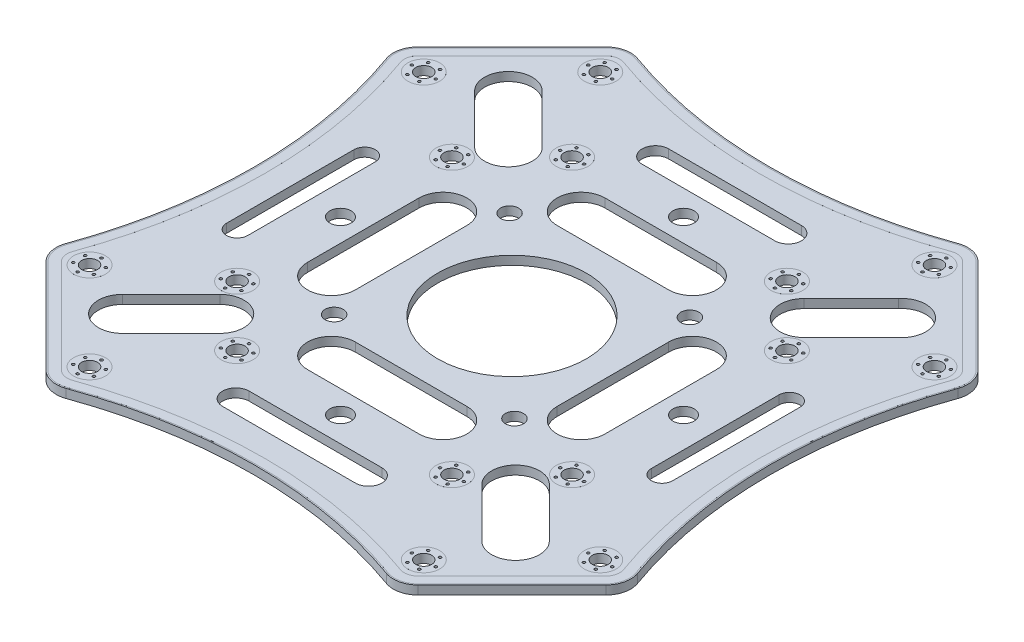
SolidWorks part; units mm, degrees
material "PLA"
ref_plane "Front Plane" through (0, 0, 0) normal (0, 0, 1) x (1, 0, 0)
ref_plane "Top Plane" through (0, 0, 0) normal (0, 1, 0) x (1, 0, 0)
ref_plane "Right Plane" through (0, 0, 0) normal (1, 0, 0) x (0, 0, -1)
sketch "Sketch1" plane through (0, 0, 0) normal (0, 1, 0) x (1, 0, 0)
  line L0 (-48.55, 0) -> (48.55, 0) construction
  line L1 (0, 48.55) -> (0, -48.55) construction
  line L2 (-30.1605, 53.8) -> (30.1605, 53.8) construction
  line L3 (0, 48.55) -> (0, 53.8) construction
  line L4 (-53.8, 30.1605) -> (-53.8, -30.1605) construction
  line L5 (-30.1605, -53.8) -> (30.1605, -53.8) construction
  line L6 (53.8, -30.1605) -> (53.8, 30.1605) construction
  line L7 (35.0464, 52.7056) -> (52.7056, 35.0464)
  line L8 (-52.7056, 35.0464) -> (-35.0464, 52.7056)
  line L9 (-52.7056, -35.0464) -> (-35.0464, -52.7056)
  line L10 (35.0464, -52.7056) -> (52.7056, -35.0464)
  line L11 (-43.876, -43.876) -> (43.876, 43.876) construction
  line L12 (-43.876, 43.876) -> (43.876, -43.876) construction
  line L13 (-31.7403, 54.075) -> (-31.7403, -54.075) construction
  line L14 (-31.7403, -54.075) -> (31.7403, -54.075) construction
  arc A0 (-30.1605, 53.8) -> (30.1605, 53.8) centre (0, 137.8088) ccw
  arc A1 (53.8, 30.1605) -> (53.8, -30.1605) centre (137.8088, 0) ccw
  arc A2 (30.1605, -53.8) -> (-30.1605, -53.8) centre (0, -137.8088) ccw
  arc A3 (-53.8, -30.1605) -> (-53.8, 30.1605) centre (-137.8088, 0) ccw
  arc A4 (-53.8, -30.1605) -> (-52.7056, -35.0464) centre (-49.3995, -31.7403) ccw
  arc A5 (-35.0464, -52.7056) -> (-30.1605, -53.8) centre (-31.7403, -49.3995) ccw
  arc A6 (30.1605, -53.8) -> (35.0464, -52.7056) centre (31.7403, -49.3995) ccw
  arc A7 (52.7056, -35.0464) -> (53.8, -30.1605) centre (49.3995, -31.7403) ccw
  arc A8 (53.8, 30.1605) -> (52.7056, 35.0464) centre (49.3995, 31.7403) ccw
  arc A9 (35.0464, 52.7056) -> (30.1605, 53.8) centre (31.7403, 49.3995) ccw
  arc A10 (-30.1605, 53.8) -> (-35.0464, 52.7056) centre (-31.7403, 49.3995) ccw
  arc A11 (-52.7056, 35.0464) -> (-53.8, 30.1605) centre (-49.3995, 31.7403) ccw
  point P2 (0, 0)
  point P6 (0, 0)
  point P34 (0, 0)
  dimension "D2" = 108.15
  dimension "D4" = 124.1
  dimension "D1" = 97.1
  dimension "D3" = 5.25
  dimension "D5" = 45
extrude "Boss-Extrude1" add sketch "Sketch1" along normal blind 0.825 and the other way blind 0.825
sketch "Sketch2" plane through (0, 0.825, 0) normal (0, 1, 0) x (1, 0, 0)
  line L0 (-12.5, -42) -> (12.5, -42)
  line L1 (-12.5, -37) -> (12.5, -37)
  line L2 (-10.5, -28) -> (10.5, -28)
  line L3 (-10.5, -19) -> (10.5, -19)
  line L4 (28, -10.5) -> (28, 10.5)
  line L5 (19, 10.5) -> (19, -10.5)
  line L6 (38, -11.7556) -> (38, 12.2444)
  line L7 (42, -11.7556) -> (42, 12.2444)
  line L8 (0, 0) -> (48.998, 0) construction
  line L9 (0, 0) -> (0, -48.55) construction
  line L10 (-10.5, 19) -> (10.5, 19)
  line L11 (-10.5, 28) -> (10.5, 28)
  line L12 (-12.5, 37) -> (12.5, 37)
  line L13 (-12.5, 42) -> (12.5, 42)
  line L14 (-42, -11.7556) -> (-42, 12.2444)
  line L15 (-38, -11.7556) -> (-38, 12.2444)
  line L16 (-19, 10.5) -> (-19, -10.5)
  line L17 (-28, -10.5) -> (-28, 10.5)
  line L18 (-33.8434, -39.5307) -> (-24.651, -30.3383)
  line L19 (-40.2073, -33.1667) -> (-31.0149, -23.9744)
  line L20 (24.654, -30.3413) -> (33.6832, -39.362)
  line L21 (31.0149, -23.9744) -> (40.2073, -33.1667)
  line L22 (33.546, 39.2333) -> (24.651, 30.3383)
  line L23 (-40.2073, 33.1667) -> (-31.0149, 23.9744)
  line L24 (31.0149, 23.9744) -> (39.9099, 32.8694)
  line L26 (-24.651, 30.3383) -> (-33.8434, 39.5307)
  arc A0 (12.5, -42) -> (12.5, -37) centre (12.5, -39.5) ccw
  arc A1 (-12.5, -37) -> (-12.5, -42) centre (-12.5, -39.5) ccw
  arc A2 (-10.5, -19) -> (-10.5, -28) centre (-10.5, -23.5) ccw
  arc A3 (10.5, -28) -> (10.5, -19) centre (10.5, -23.5) ccw
  arc A4 (38, -11.7556) -> (42, -11.7556) centre (40, -11.7556) ccw
  arc A5 (19, -10.5) -> (28, -10.5) centre (23.5, -10.5) ccw
  arc A6 (42, 12.2444) -> (38, 12.2444) centre (40, 12.2444) ccw
  arc A7 (28, 10.5) -> (19, 10.5) centre (23.5, 10.5) ccw
  arc A8 (53.943, 29.5883) -> (53.943, -29.5883) centre (139.9907, 0) ccw construction
  arc A9 (30.1605, -53.8) -> (-30.1605, -53.8) centre (0, -137.8088) ccw construction
  arc A10 (10.5, 28) -> (10.5, 19) centre (10.5, 23.5) cw
  arc A11 (-10.5, 19) -> (-10.5, 28) centre (-10.5, 23.5) cw
  arc A12 (-12.5, 37) -> (-12.5, 42) centre (-12.5, 39.5) cw
  arc A13 (12.5, 42) -> (12.5, 37) centre (12.5, 39.5) cw
  arc A14 (-28, 10.5) -> (-19, 10.5) centre (-23.5, 10.5) cw
  arc A15 (-42, 12.2444) -> (-38, 12.2444) centre (-40, 12.2444) cw
  arc A16 (-19, -10.5) -> (-28, -10.5) centre (-23.5, -10.5) cw
  arc A17 (-38, -11.7556) -> (-42, -11.7556) centre (-40, -11.7556) cw
  arc A18 (-24.651, -30.3383) -> (-31.0149, -23.9744) centre (-27.833, -27.1563) ccw
  arc A19 (-40.2073, -33.1667) -> (-33.8434, -39.5307) centre (-37.0253, -36.3487) ccw
  arc A20 (33.6832, -39.362) -> (40.2073, -33.1667) centre (37.0253, -36.3487) ccw
  arc A21 (31.0149, -23.9744) -> (24.654, -30.3413) centre (27.833, -27.1563) ccw
  arc A22 (-31.0149, 23.9744) -> (-24.651, 30.3383) centre (-27.833, 27.1563) ccw
  arc A23 (-33.8434, 39.5307) -> (-40.2073, 33.1667) centre (-37.0253, 36.3487) ccw
  arc A24 (39.9099, 32.8694) -> (33.546, 39.2333) centre (37.0253, 36.3487) ccw
  arc A25 (24.651, 30.3383) -> (31.0149, 23.9744) centre (27.833, 27.1563) ccw
  circle A26 centre (0, 0) radius 14
extrude "Cut-Extrude1" cut sketch "Sketch2" against normal up to surface (1.65 mm away) up to face at (0, -0.825, 0)
sketch "Sketch3" plane through (0, 0.825, 0) normal (0, 1, 0) x (1, 0, 0)
  line L0 (-48.0833, -31.4663) -> (-31.4663, -48.0833) construction
  line L1 (-52.7056, -35.0464) -> (-35.0464, -52.7056) construction
  line L2 (-39.7748, -39.7748) -> (-43.876, -43.876) construction
  line L3 (43.876, -43.876) -> (39.7748, -39.7748) construction
  line L4 (31.4663, -48.0833) -> (48.0833, -31.4663) construction
  line L5 (43.876, 43.876) -> (39.7748, 39.7748) construction
  line L6 (31.4663, 48.0833) -> (48.0833, 31.4663) construction
  line L7 (-43.876, 43.876) -> (-39.7748, 39.7748) construction
  line L8 (-31.4663, 48.0833) -> (-48.0833, 31.4663) construction
  line L9 (-35.0464, 52.7056) -> (-52.7056, 35.0464) construction
  line L10 (52.7056, 35.0464) -> (35.0464, 52.7056) construction
  line L11 (35.0464, -52.7056) -> (52.7056, -35.0464) construction
  line L12 (-31.5403, -20.2266) -> (-20.2266, -31.5403) construction
  line L13 (31.5403, -20.2266) -> (20.2266, -31.5403) construction
  line L14 (-31.5403, 20.2266) -> (-20.2266, 31.5403) construction
  line L15 (20.2266, 31.5403) -> (31.5403, 20.2266) construction
  line L16 (-25.8834, -25.8834) -> (-39.7748, -39.7748) construction
  line L17 (-39.7748, 39.7748) -> (-25.8834, 25.8834) construction
  line L18 (39.7748, 39.7748) -> (25.8834, 25.8834) construction
  line L19 (25.8834, -25.8834) -> (39.7748, -39.7748) construction
  line L20 (-20.2266, -31.5403) -> (-31.4663, -48.0833) construction
  line L21 (-31.5403, -20.2266) -> (-48.0833, -31.4663) construction
  line L22 (0, 0) -> (-24.651, 23.9744) construction
  line L23 (0, 0) -> (24.651, 23.9744) construction
  line L24 (0, 0) -> (24.6495, -23.9759) construction
  line L25 (0, 0) -> (-24.651, -23.9744) construction
  circle A0 centre (-48.0833, -31.4663) radius 1.5
  circle A1 centre (-31.4663, -48.0833) radius 1.5
  circle A2 centre (31.4663, -48.0833) radius 1.5
  circle A3 centre (48.0833, -31.4663) radius 1.5
  circle A4 centre (48.0833, 31.4663) radius 1.5
  circle A5 centre (31.4663, 48.0833) radius 1.5
  circle A6 centre (-31.4663, 48.0833) radius 1.5
  circle A7 centre (-48.0833, 31.4663) radius 1.5
  circle A8 centre (-31.5403, -20.2266) radius 1.5
  circle A9 centre (-20.2266, -31.5403) radius 1.5
  circle A10 centre (-31.5403, 20.2266) radius 1.5
  circle A11 centre (-20.2266, 31.5403) radius 1.5
  circle A12 centre (20.2266, 31.5403) radius 1.5
  circle A13 centre (31.5403, 20.2266) radius 1.5
  circle A14 centre (31.5403, -20.2266) radius 1.5
  circle A15 centre (20.2266, -31.5403) radius 1.5
  circle A16 centre (0, -32.3) radius 2
  circle A17 centre (-32.3, 0) radius 2
  circle A18 centre (32.3, 0) radius 2
  circle A19 centre (0, 32.3) radius 2
  circle A20 centre (-16.9804, 16.5143) radius 1.7
  arc A21 (-31.0149, 23.9744) -> (-24.651, 30.3383) centre (-27.833, 27.1563) ccw construction
  arc A22 (31.0149, -23.9744) -> (24.654, -30.3413) centre (27.833, -27.1563) ccw construction
  circle A23 centre (16.9804, 16.5143) radius 1.7
  arc A24 (24.651, 30.3383) -> (31.0149, 23.9744) centre (27.833, 27.1563) ccw construction
  arc A25 (-24.651, -30.3383) -> (-31.0149, -23.9744) centre (-27.833, -27.1563) ccw construction
  circle A26 centre (-16.9804, -16.5143) radius 1.7
  circle A27 centre (16.9794, -16.5153) radius 1.7
  point P70 (-24.651, 23.9744)
  point P79 (24.651, 23.9744)
  dimension "D3" = 3
  dimension "D4" = 20
  dimension "D6" = 4
  dimension "D8" = 10.7
  dimension "D9" = 3.4
  dimension "D11" = 10.7
  dimension "D12" = 10.7
  dimension "D1" = 23.5
  dimension "D2" = 5.8
  dimension "D5" = 16
  dimension "D7" = 10.7
extrude "Cut-Extrude2" cut sketch "Sketch3" against normal up to surface (1.65 mm away) up to face at (32.3883, -0.825, 31.7525)
sketch "Sketch4" plane through (0, 0.825, 0) normal (0, 1, 0) x (1, 0, 0)
  line L18 (34.8696, -52.5288) -> (52.5288, -34.8696)
  line L19 (35.0464, -52.7056) -> (52.7056, -35.0464) construction
  line L20 (34.8696, 52.5288) -> (52.5288, 34.8696)
  line L21 (52.7056, 35.0464) -> (35.0464, 52.7056) construction
  line L22 (-52.5288, 34.8696) -> (-34.8696, 52.5288)
  line L23 (-35.0464, 52.7056) -> (-52.7056, 35.0464) construction
  line L24 (-52.5288, -34.8696) -> (-34.8696, -52.5288)
  line L25 (-52.7056, -35.0464) -> (-35.0464, -52.7056) construction
  line L26 (-51.256, 33.5968) -> (-33.5968, 51.256)
  line L27 (33.5968, 51.256) -> (51.256, 33.5968)
  line L28 (33.5968, -51.256) -> (51.256, -33.5968)
  line L29 (-51.256, -33.5968) -> (-33.5968, -51.256)
  line L30 (-31.4663, -45.8333) -> (-31.4663, -46.5833) construction
  line L31 (-29.5177, -46.9583) -> (-31.4663, -45.8333) construction
  line L32 (-31.4663, -45.8333) -> (-33.4148, -46.9583) construction
  line L33 (-33.4148, -46.9583) -> (-33.4148, -49.2083) construction
  line L34 (-33.4148, -49.2083) -> (-31.4663, -50.3333) construction
  line L35 (-31.4663, -50.3333) -> (-29.5177, -49.2083) construction
  line L36 (-29.5177, -49.2083) -> (-29.5177, -46.9583) construction
  line L37 (-31.4663, -45.8333) -> (-31.4663, -45.0833) construction
  line L39 (-48.0833, -29.2163) -> (-50.0318, -30.3413) construction
  line L40 (-50.0318, -30.3413) -> (-50.0318, -32.5913) construction
  line L41 (-50.0318, -32.5913) -> (-48.0833, -33.7163) construction
  line L42 (-48.0833, -33.7163) -> (-46.1347, -32.5913) construction
  line L43 (-46.1347, -32.5913) -> (-46.1347, -30.3413) construction
  line L44 (-46.1347, -30.3413) -> (-48.0833, -29.2163) construction
  line L45 (-31.5403, -17.9766) -> (-33.4888, -19.1016) construction
  line L46 (-33.4888, -19.1016) -> (-33.4888, -21.3516) construction
  line L47 (-33.4888, -21.3516) -> (-31.5403, -22.4766) construction
  line L48 (-31.5403, -22.4766) -> (-29.5917, -21.3516) construction
  line L49 (-29.5917, -21.3516) -> (-29.5917, -19.1016) construction
  line L50 (-29.5917, -19.1016) -> (-31.5403, -17.9766) construction
  line L51 (-20.2266, -29.2903) -> (-22.1751, -30.4153) construction
  line L52 (-22.1751, -30.4153) -> (-22.1751, -32.6653) construction
  line L53 (-22.1751, -32.6653) -> (-20.2266, -33.7903) construction
  line L54 (-20.2266, -33.7903) -> (-18.278, -32.6653) construction
  line L55 (-18.278, -32.6653) -> (-18.278, -30.4153) construction
  line L56 (-18.278, -30.4153) -> (-20.2266, -29.2903) construction
  line L57 (20.2266, 33.7903) -> (18.278, 32.6653) construction
  line L58 (18.278, 32.6653) -> (18.278, 30.4153) construction
  line L59 (18.278, 30.4153) -> (20.2266, 29.2903) construction
  line L60 (20.2266, 29.2903) -> (22.1751, 30.4153) construction
  line L61 (22.1751, 30.4153) -> (22.1751, 32.6653) construction
  line L62 (22.1751, 32.6653) -> (20.2266, 33.7903) construction
  line L63 (31.5403, 22.4766) -> (29.5917, 21.3516) construction
  line L64 (29.5917, 21.3516) -> (29.5917, 19.1016) construction
  line L65 (29.5917, 19.1016) -> (31.5403, 17.9766) construction
  line L66 (31.5403, 17.9766) -> (33.4888, 19.1016) construction
  line L67 (33.4888, 19.1016) -> (33.4888, 21.3516) construction
  line L68 (33.4888, 21.3516) -> (31.5403, 22.4766) construction
  line L69 (48.0833, 33.7163) -> (46.1347, 32.5913) construction
  line L70 (46.1347, 32.5913) -> (46.1347, 30.3413) construction
  line L71 (46.1347, 30.3413) -> (48.0833, 29.2163) construction
  line L72 (48.0833, 29.2163) -> (50.0318, 30.3413) construction
  line L73 (50.0318, 30.3413) -> (50.0318, 32.5913) construction
  line L74 (50.0318, 32.5913) -> (48.0833, 33.7163) construction
  line L75 (31.4663, 50.3333) -> (29.5177, 49.2083) construction
  line L76 (29.5177, 49.2083) -> (29.5177, 46.9583) construction
  line L77 (29.5177, 46.9583) -> (31.4663, 45.8333) construction
  line L78 (31.4663, 45.8333) -> (33.4148, 46.9583) construction
  line L79 (33.4148, 46.9583) -> (33.4148, 49.2083) construction
  line L80 (33.4148, 49.2083) -> (31.4663, 50.3333) construction
  line L81 (-50.3333, 31.4663) -> (-49.2083, 29.5177) construction
  line L82 (-49.2083, 29.5177) -> (-46.9583, 29.5177) construction
  line L83 (-46.9583, 29.5177) -> (-45.8333, 31.4663) construction
  line L84 (-45.8333, 31.4663) -> (-46.9583, 33.4148) construction
  line L85 (-46.9583, 33.4148) -> (-49.2083, 33.4148) construction
  line L86 (-49.2083, 33.4148) -> (-50.3333, 31.4663) construction
  line L87 (-33.7903, 20.2266) -> (-32.6653, 18.278) construction
  line L88 (-32.6653, 18.278) -> (-30.4153, 18.278) construction
  line L89 (-30.4153, 18.278) -> (-29.2903, 20.2266) construction
  line L90 (-29.2903, 20.2266) -> (-30.4153, 22.1751) construction
  line L91 (-30.4153, 22.1751) -> (-32.6653, 22.1751) construction
  line L92 (-32.6653, 22.1751) -> (-33.7903, 20.2266) construction
  line L93 (-22.4766, 31.5403) -> (-21.3516, 29.5917) construction
  line L94 (-21.3516, 29.5917) -> (-19.1016, 29.5917) construction
  line L95 (-19.1016, 29.5917) -> (-17.9766, 31.5403) construction
  line L96 (-17.9766, 31.5403) -> (-19.1016, 33.4888) construction
  line L97 (-19.1016, 33.4888) -> (-21.3516, 33.4888) construction
  line L98 (-21.3516, 33.4888) -> (-22.4766, 31.5403) construction
  line L99 (-29.2163, 48.0833) -> (-30.3413, 50.0318) construction
  line L100 (-30.3413, 50.0318) -> (-32.5913, 50.0318) construction
  line L101 (-32.5913, 50.0318) -> (-33.7163, 48.0833) construction
  line L102 (-33.7163, 48.0833) -> (-32.5913, 46.1347) construction
  line L103 (-32.5913, 46.1347) -> (-30.3413, 46.1347) construction
  line L104 (-30.3413, 46.1347) -> (-29.2163, 48.0833) construction
  line L105 (22.4766, -31.5403) -> (21.3516, -29.5917) construction
  line L106 (21.3516, -29.5917) -> (19.1016, -29.5917) construction
  line L107 (19.1016, -29.5917) -> (17.9766, -31.5403) construction
  line L108 (17.9766, -31.5403) -> (19.1016, -33.4888) construction
  line L109 (19.1016, -33.4888) -> (21.3516, -33.4888) construction
  line L110 (21.3516, -33.4888) -> (22.4766, -31.5403) construction
  line L111 (33.7903, -20.2266) -> (32.6653, -18.278) construction
  line L112 (32.6653, -18.278) -> (30.4153, -18.278) construction
  line L113 (30.4153, -18.278) -> (29.2903, -20.2266) construction
  line L114 (29.2903, -20.2266) -> (30.4153, -22.1751) construction
  line L115 (30.4153, -22.1751) -> (32.6653, -22.1751) construction
  line L116 (32.6653, -22.1751) -> (33.7903, -20.2266) construction
  line L117 (33.7163, -48.0833) -> (32.5913, -46.1347) construction
  line L118 (32.5913, -46.1347) -> (30.3413, -46.1347) construction
  line L119 (30.3413, -46.1347) -> (29.2163, -48.0833) construction
  line L120 (29.2163, -48.0833) -> (30.3413, -50.0318) construction
  line L121 (30.3413, -50.0318) -> (32.5913, -50.0318) construction
  line L122 (32.5913, -50.0318) -> (33.7163, -48.0833) construction
  line L123 (50.3333, -31.4663) -> (49.2083, -29.5177) construction
  line L124 (49.2083, -29.5177) -> (46.9583, -29.5177) construction
  line L125 (46.9583, -29.5177) -> (45.8333, -31.4663) construction
  line L126 (45.8333, -31.4663) -> (46.9583, -33.4148) construction
  line L127 (46.9583, -33.4148) -> (49.2083, -33.4148) construction
  line L128 (49.2083, -33.4148) -> (50.3333, -31.4663) construction
  arc A24 (30.245, -53.5647) -> (-30.245, -53.5647) centre (0, -137.8088) ccw
  arc A25 (30.1605, -53.8) -> (-30.1605, -53.8) centre (0, -137.8088) ccw construction
  arc A26 (-53.5647, -30.245) -> (-53.5647, 30.245) centre (-137.8088, 0) ccw
  arc A27 (-30.245, 53.5647) -> (30.245, 53.5647) centre (0, 137.8088) ccw
  arc A28 (53.5647, 30.245) -> (53.5647, -30.245) centre (137.8088, 0) ccw
  arc A29 (53.8, 30.1605) -> (53.8, -30.1605) centre (137.8088, 0) ccw construction
  arc A30 (-30.1605, 53.8) -> (30.1605, 53.8) centre (0, 137.8088) ccw construction
  arc A31 (-53.8, -30.1605) -> (-53.8, 30.1605) centre (-137.8088, 0) ccw construction
  arc A32 (34.8696, 52.5288) -> (30.245, 53.5647) centre (31.7403, 49.3995) ccw
  arc A33 (35.0464, 52.7056) -> (30.1605, 53.8) centre (31.7403, 49.3995) ccw construction
  arc A34 (53.5647, 30.245) -> (52.5288, 34.8696) centre (49.3995, 31.7403) ccw
  arc A35 (53.8, 30.1605) -> (52.7056, 35.0464) centre (49.3995, 31.7403) ccw construction
  arc A36 (52.5288, -34.8696) -> (53.5647, -30.245) centre (49.3995, -31.7403) ccw
  arc A37 (52.7056, -35.0464) -> (53.8, -30.1605) centre (49.3995, -31.7403) ccw construction
  arc A38 (30.245, -53.5647) -> (34.8696, -52.5288) centre (31.7403, -49.3995) ccw
  arc A39 (30.1605, -53.8) -> (35.0464, -52.7056) centre (31.7403, -49.3995) ccw construction
  arc A40 (-34.8696, -52.5288) -> (-30.245, -53.5647) centre (-31.7403, -49.3995) ccw
  arc A41 (-35.0464, -52.7056) -> (-30.1605, -53.8) centre (-31.7403, -49.3995) ccw construction
  arc A42 (-53.5647, -30.245) -> (-52.5288, -34.8696) centre (-49.3995, -31.7403) ccw
  arc A43 (-53.8, -30.1605) -> (-52.7056, -35.0464) centre (-49.3995, -31.7403) ccw construction
  arc A44 (-52.5288, 34.8696) -> (-53.5647, 30.245) centre (-49.3995, 31.7403) ccw
  arc A45 (-52.7056, 35.0464) -> (-53.8, 30.1605) centre (-49.3995, 31.7403) ccw construction
  arc A46 (-30.245, 53.5647) -> (-34.8696, 52.5288) centre (-31.7403, 49.3995) ccw
  arc A47 (-30.1605, 53.8) -> (-35.0464, 52.7056) centre (-31.7403, 49.3995) ccw construction
  arc A48 (-51.8706, -30.8532) -> (-51.8706, 30.8532) centre (-137.8088, 0) ccw
  arc A49 (-51.256, 33.5968) -> (-51.8706, 30.8532) centre (-49.3995, 31.7403) ccw
  arc A50 (-30.8532, 51.8706) -> (-33.5968, 51.256) centre (-31.7403, 49.3995) ccw
  arc A51 (-30.8532, 51.8706) -> (30.8532, 51.8706) centre (0, 137.8088) ccw
  arc A52 (33.5968, 51.256) -> (30.8532, 51.8706) centre (31.7403, 49.3995) ccw
  arc A53 (51.8706, 30.8532) -> (51.256, 33.5968) centre (49.3995, 31.7403) ccw
  arc A54 (51.8706, 30.8532) -> (51.8706, -30.8532) centre (137.8088, 0) ccw
  arc A55 (51.256, -33.5968) -> (51.8706, -30.8532) centre (49.3995, -31.7403) ccw
  arc A56 (30.8532, -51.8706) -> (33.5968, -51.256) centre (31.7403, -49.3995) ccw
  arc A57 (30.8532, -51.8706) -> (-30.8532, -51.8706) centre (0, -137.8088) ccw
  arc A58 (-33.5968, -51.256) -> (-30.8532, -51.8706) centre (-31.7403, -49.3995) ccw
  arc A59 (-51.8706, -30.8532) -> (-51.256, -33.5968) centre (-49.3995, -31.7403) ccw
  circle A60 centre (-31.4663, -48.0833) radius 3
  circle A61 centre (-48.0833, -31.4663) radius 3
  circle A62 centre (-31.5403, -20.2266) radius 3
  circle A63 centre (-20.2266, -31.5403) radius 3
  circle A64 centre (-48.0833, 31.4663) radius 3
  circle A65 centre (-31.5403, 20.2266) radius 3
  circle A66 centre (-20.2266, 31.5403) radius 3
  circle A67 centre (-31.4663, 48.0833) radius 3
  circle A68 centre (20.2266, 31.5403) radius 3
  circle A69 centre (31.4663, 48.0833) radius 3
  circle A70 centre (48.0833, 31.4663) radius 3
  circle A71 centre (31.5403, 20.2266) radius 3
  circle A72 centre (20.2266, -31.5403) radius 3
  circle A73 centre (31.5403, -20.2266) radius 3
  circle A74 centre (48.0833, -31.4663) radius 3
  circle A75 centre (31.4663, -48.0833) radius 3
  circle A76 centre (-31.4663, -48.0833) radius 1.5 construction
  circle A77 centre (-48.0833, -31.4663) radius 1.5 construction
  circle A78 centre (-31.5403, -20.2266) radius 1.5 construction
  circle A79 centre (-20.2266, -31.5403) radius 1.5 construction
  circle A80 centre (20.2266, -31.5403) radius 1.5 construction
  circle A81 centre (31.4663, -48.0833) radius 1.5 construction
  circle A82 centre (48.0833, -31.4663) radius 1.5 construction
  circle A83 centre (31.5403, -20.2266) radius 1.5 construction
  circle A84 centre (48.0833, 31.4663) radius 1.5 construction
  circle A85 centre (31.5403, 20.2266) radius 1.5 construction
  circle A86 centre (20.2266, 31.5403) radius 1.5 construction
  circle A87 centre (31.4663, 48.0833) radius 1.5 construction
  circle A88 centre (-20.2266, 31.5403) radius 1.5 construction
  circle A89 centre (-31.5403, 20.2266) radius 1.5 construction
  circle A90 centre (-48.0833, 31.4663) radius 1.5 construction
  circle A91 centre (-31.4663, 48.0833) radius 1.5 construction
  circle A92 centre (-48.0833, -31.4663) radius 1.5
  circle A93 centre (-31.4663, -48.0833) radius 1.5
  circle A94 centre (-20.2266, -31.5403) radius 1.5
  circle A95 centre (-31.5403, -20.2266) radius 1.5
  circle A96 centre (-48.0833, 31.4663) radius 1.5
  circle A97 centre (-31.5403, 20.2266) radius 1.5
  circle A98 centre (-20.2266, 31.5403) radius 1.5
  circle A99 centre (-31.4663, 48.0833) radius 1.5
  circle A100 centre (20.2266, 31.5403) radius 1.5
  circle A101 centre (31.4663, 48.0833) radius 1.5
  circle A102 centre (48.0833, 31.4663) radius 1.5
  circle A103 centre (31.5403, 20.2266) radius 1.5
  circle A104 centre (31.5403, -20.2266) radius 1.5
  circle A105 centre (20.2266, -31.5403) radius 1.5
  circle A106 centre (48.0833, -31.4663) radius 1.5
  circle A107 centre (31.4663, -48.0833) radius 1.5
  circle A108 centre (-31.4663, -48.0833) radius 1.9486 construction
  circle A109 centre (-48.0833, -31.4663) radius 1.9486 construction
  circle A110 centre (-31.5403, -20.2266) radius 1.9486 construction
  circle A111 centre (-20.2266, -31.5403) radius 1.9486 construction
  circle A112 centre (-31.4663, -50.3333) radius 0.25
  circle A113 centre (-29.5177, -49.2083) radius 0.25
  circle A114 centre (-29.5177, -46.9583) radius 0.25
  circle A115 centre (-31.4663, -45.8333) radius 0.25
  circle A116 centre (-33.4148, -46.9583) radius 0.25
  circle A117 centre (-33.4148, -49.2083) radius 0.25
  circle A118 centre (-48.0833, -33.7163) radius 0.25
  circle A119 centre (-46.1347, -32.5913) radius 0.25
  circle A120 centre (-46.1347, -30.3413) radius 0.25
  circle A121 centre (-48.0833, -29.2163) radius 0.25
  circle A122 centre (-50.0318, -30.3413) radius 0.25
  circle A123 centre (-50.0318, -32.5913) radius 0.25
  circle A124 centre (-31.5403, -22.4766) radius 0.25
  circle A125 centre (-29.5917, -21.3516) radius 0.25
  circle A126 centre (-29.5917, -19.1016) radius 0.25
  circle A127 centre (-31.5403, -17.9766) radius 0.25
  circle A128 centre (-33.4888, -19.1016) radius 0.25
  circle A129 centre (-33.4888, -21.3516) radius 0.25
  circle A130 centre (-20.2266, -33.7903) radius 0.25
  circle A131 centre (-18.278, -32.6653) radius 0.25
  circle A132 centre (-18.278, -30.4153) radius 0.25
  circle A133 centre (-20.2266, -29.2903) radius 0.25
  circle A134 centre (-22.1751, -30.4153) radius 0.25
  circle A135 centre (-22.1751, -32.6653) radius 0.25
  circle A136 centre (20.2266, 31.5403) radius 1.9486 construction
  circle A137 centre (31.5403, 20.2266) radius 1.9486 construction
  circle A138 centre (48.0833, 31.4663) radius 1.9486 construction
  circle A139 centre (31.4663, 48.0833) radius 1.9486 construction
  circle A140 centre (20.2266, 29.2903) radius 0.25
  circle A141 centre (22.1751, 30.4153) radius 0.25
  circle A142 centre (22.1751, 32.6653) radius 0.25
  circle A143 centre (18.278, 30.4153) radius 0.25
  circle A144 centre (18.278, 32.6653) radius 0.25
  circle A145 centre (20.2266, 33.7903) radius 0.25
  circle A146 centre (31.4663, 45.8333) radius 0.25
  circle A147 centre (29.5177, 46.9583) radius 0.25
  circle A148 centre (29.5177, 49.2083) radius 0.25
  circle A149 centre (31.4663, 50.3333) radius 0.25
  circle A150 centre (33.4148, 49.2083) radius 0.25
  circle A151 centre (33.4148, 46.9583) radius 0.25
  circle A152 centre (29.5917, 21.3516) radius 0.25
  circle A153 centre (29.5917, 19.1016) radius 0.25
  circle A154 centre (31.5403, 17.9766) radius 0.25
  circle A155 centre (33.4888, 19.1016) radius 0.25
  circle A156 centre (33.4888, 21.3516) radius 0.25
  circle A157 centre (31.5403, 22.4766) radius 0.25
  circle A158 centre (48.0833, 29.2163) radius 0.25
  circle A159 centre (46.1347, 30.3413) radius 0.25
  circle A160 centre (50.0318, 30.3413) radius 0.25
  circle A161 centre (50.0318, 32.5913) radius 0.25
  circle A162 centre (48.0833, 33.7163) radius 0.25
  circle A163 centre (46.1347, 32.5913) radius 0.25
  circle A164 centre (-48.0833, 31.4663) radius 1.9486 construction
  circle A165 centre (-31.5403, 20.2266) radius 1.9486 construction
  circle A166 centre (-20.2266, 31.5403) radius 1.9486 construction
  circle A167 centre (-31.4663, 48.0833) radius 1.9486 construction
  circle A168 centre (-46.9583, 29.5177) radius 0.25
  circle A169 centre (-45.8333, 31.4663) radius 0.25
  circle A170 centre (-46.9583, 33.4148) radius 0.25
  circle A171 centre (-49.2083, 33.4148) radius 0.25
  circle A172 centre (-50.3333, 31.4663) radius 0.25
  circle A173 centre (-49.2083, 29.5177) radius 0.25
  circle A174 centre (-32.6653, 18.278) radius 0.25
  circle A175 centre (-33.7903, 20.2266) radius 0.25
  circle A176 centre (-32.6653, 22.1751) radius 0.25
  circle A177 centre (-30.4153, 22.1751) radius 0.25
  circle A178 centre (-29.2903, 20.2266) radius 0.25
  circle A179 centre (-30.4153, 18.278) radius 0.25
  circle A180 centre (-19.1016, 29.5917) radius 0.25
  circle A181 centre (-21.3516, 29.5917) radius 0.25
  circle A182 centre (-22.4766, 31.5403) radius 0.25
  circle A183 centre (-21.3516, 33.4888) radius 0.25
  circle A184 centre (-19.1016, 33.4888) radius 0.25
  circle A185 centre (-17.9766, 31.5403) radius 0.25
  circle A186 centre (-32.5913, 46.1347) radius 0.25
  circle A187 centre (-33.7163, 48.0833) radius 0.25
  circle A188 centre (-32.5913, 50.0318) radius 0.25
  circle A189 centre (-30.3413, 50.0318) radius 0.25
  circle A190 centre (-29.2163, 48.0833) radius 0.25
  circle A191 centre (-30.3413, 46.1347) radius 0.25
  circle A192 centre (20.2266, -31.5403) radius 1.9486 construction
  circle A193 centre (31.5403, -20.2266) radius 1.9486 construction
  circle A194 centre (31.4663, -48.0833) radius 1.9486 construction
  circle A195 centre (48.0833, -31.4663) radius 1.9486 construction
  circle A196 centre (19.1016, -33.4888) radius 0.25
  circle A197 centre (21.3516, -33.4888) radius 0.25
  circle A198 centre (22.4766, -31.5403) radius 0.25
  circle A199 centre (21.3516, -29.5917) radius 0.25
  circle A200 centre (19.1016, -29.5917) radius 0.25
  circle A201 centre (17.9766, -31.5403) radius 0.25
  circle A202 centre (30.3413, -50.0318) radius 0.25
  circle A203 centre (29.2163, -48.0833) radius 0.25
  circle A204 centre (30.3413, -46.1347) radius 0.25
  circle A205 centre (32.5913, -46.1347) radius 0.25
  circle A206 centre (33.7163, -48.0833) radius 0.25
  circle A207 centre (32.5913, -50.0318) radius 0.25
  circle A208 centre (46.9583, -33.4148) radius 0.25
  circle A209 centre (45.8333, -31.4663) radius 0.25
  circle A210 centre (46.9583, -29.5177) radius 0.25
  circle A211 centre (49.2083, -29.5177) radius 0.25
  circle A212 centre (50.3333, -31.4663) radius 0.25
  circle A213 centre (49.2083, -33.4148) radius 0.25
  circle A214 centre (30.4153, -22.1751) radius 0.25
  circle A215 centre (29.2903, -20.2266) radius 0.25
  circle A216 centre (30.4153, -18.278) radius 0.25
  circle A217 centre (32.6653, -18.278) radius 0.25
  circle A218 centre (33.7903, -20.2266) radius 0.25
  circle A219 centre (32.6653, -22.1751) radius 0.25
  dimension "D5" = 0.25
  dimension "D7" = 6
  dimension "D8" = 0.5
  dimension "D6" = 1.8
extrude "Boss-Extrude2" add sketch "Sketch4" along normal blind 0.001 contours A27 A46 L22 A44 A26 A42 L24 A40 A24 A38 L18 A36 A28 A34 L20 A32 A59 A48 A49 L26 A50 A51 A52 L27 A53 A54 A55 L28 A56 A57 A58 L29 | A61 A92 | A60 A93 | A63 A94 | A62 A95 | A75 A107 | A72 A105 | A73 A104 | A74 A106 | A71 A103 | A70 A102 | A68 A100 | A69 A101 | A64 A96 | A65 A97 | A66 A98 | A67 A99 region at (32.3749, 0.825, 52.2324) region at (-34.3814, 0.825, 48.0833) region at (-50.9984, 0.825, 31.4663) region at (-34.4554, 0.825, 20.2266) region at (-23.1417, 0.825, 31.5403) region at (-50.9984, 0.825, -31.4663) region at (-34.4554, 0.825, -20.2266) region at (-23.1417, 0.825, -31.5403) region at (-34.3814, 0.825, -48.0833) region at (17.3114, 0.825, -31.5403) region at (28.5511, 0.825, -48.0833) region at (45.1681, 0.825, -31.4663) region at (28.6251, 0.825, -20.2266) region at (17.3114, 0.825, 31.5403) region at (28.6251, 0.825, 20.2266) region at (45.1681, 0.825, 31.4663) region at (28.5511, 0.825, 48.0833)
mirror "Mirror2" about plane through (0, 0, 0) normal (0, 1, 0) of "Boss-Extrude2"
sketch "Sketch5" plane through (0, 0.825, 0) normal (0, 1, 0) x (1, 0, 0)
  circle A0 centre (-31.4663, -45.8333) radius 0.25
  circle A1 centre (-29.5177, -46.9583) radius 0.25
  circle A2 centre (-29.5177, -49.2083) radius 0.25
  circle A3 centre (-31.4663, -50.3333) radius 0.25
  circle A4 centre (-33.4148, -49.2083) radius 0.25
  circle A5 centre (-33.4148, -46.9583) radius 0.25
  circle A6 centre (-48.0833, -33.7163) radius 0.25
  circle A7 centre (-50.0318, -32.5913) radius 0.25
  circle A8 centre (-50.0318, -30.3413) radius 0.25
  circle A9 centre (-48.0833, -29.2163) radius 0.25
  circle A10 centre (-46.1347, -30.3413) radius 0.25
  circle A11 centre (-46.1347, -32.5913) radius 0.25
  circle A12 centre (-33.4888, -21.3516) radius 0.25
  circle A13 centre (-33.4888, -19.1016) radius 0.25
  circle A14 centre (-31.5403, -17.9766) radius 0.25
  circle A15 centre (-29.5917, -19.1016) radius 0.25
  circle A16 centre (-29.5917, -21.3516) radius 0.25
  circle A17 centre (-31.5403, -22.4766) radius 0.25
  circle A18 centre (-22.1751, -30.4153) radius 0.25
  circle A19 centre (-22.1751, -32.6653) radius 0.25
  circle A20 centre (-20.2266, -33.7903) radius 0.25
  circle A21 centre (-18.278, -32.6653) radius 0.25
  circle A22 centre (-18.278, -30.4153) radius 0.25
  circle A23 centre (-20.2266, -29.2903) radius 0.25
  circle A24 centre (-31.4663, -50.3333) radius 0.25 construction
  circle A25 centre (-33.4148, -49.2083) radius 0.25 construction
  circle A26 centre (-33.4148, -46.9583) radius 0.25 construction
  circle A27 centre (-31.4663, -45.8333) radius 0.25 construction
  circle A28 centre (-29.5177, -46.9583) radius 0.25 construction
  circle A29 centre (-29.5177, -49.2083) radius 0.25 construction
  circle A30 centre (-48.0833, -33.7163) radius 0.25 construction
  circle A31 centre (-50.0318, -32.5913) radius 0.25 construction
  circle A32 centre (-50.0318, -30.3413) radius 0.25 construction
  circle A33 centre (-48.0833, -29.2163) radius 0.25 construction
  circle A34 centre (-46.1347, -30.3413) radius 0.25 construction
  circle A35 centre (-46.1347, -32.5913) radius 0.25 construction
  circle A36 centre (-31.5403, -22.4766) radius 0.25 construction
  circle A37 centre (-33.4888, -21.3516) radius 0.25 construction
  circle A38 centre (-33.4888, -19.1016) radius 0.25 construction
  circle A39 centre (-31.5403, -17.9766) radius 0.25 construction
  circle A40 centre (-29.5917, -19.1016) radius 0.25 construction
  circle A41 centre (-29.5917, -21.3516) radius 0.25 construction
  circle A42 centre (-22.1751, -32.6653) radius 0.25 construction
  circle A43 centre (-22.1751, -30.4153) radius 0.25 construction
  circle A44 centre (-20.2266, -29.2903) radius 0.25 construction
  circle A45 centre (-18.278, -30.4153) radius 0.25 construction
  circle A46 centre (-18.278, -32.6653) radius 0.25 construction
  circle A47 centre (-20.2266, -33.7903) radius 0.25 construction
  circle A48 centre (19.1016, -33.4888) radius 0.25
  circle A49 centre (17.9766, -31.5403) radius 0.25
  circle A50 centre (19.1016, -29.5917) radius 0.25
  circle A51 centre (21.3516, -29.5917) radius 0.25
  circle A52 centre (22.4766, -31.5403) radius 0.25
  circle A53 centre (21.3516, -33.4888) radius 0.25
  circle A54 centre (19.1016, -33.4888) radius 0.25 construction
  circle A55 centre (21.3516, -33.4888) radius 0.25 construction
  circle A56 centre (17.9766, -31.5403) radius 0.25 construction
  circle A57 centre (19.1016, -29.5917) radius 0.25 construction
  circle A58 centre (21.3516, -29.5917) radius 0.25 construction
  circle A59 centre (22.4766, -31.5403) radius 0.25 construction
  circle A60 centre (29.2903, -20.2266) radius 0.25
  circle A61 centre (30.4153, -18.278) radius 0.25
  circle A62 centre (32.6653, -18.278) radius 0.25
  circle A63 centre (30.4153, -22.1751) radius 0.25
  circle A64 centre (32.6653, -22.1751) radius 0.25
  circle A65 centre (33.7903, -20.2266) radius 0.25
  circle A66 centre (29.2903, -20.2266) radius 0.25 construction
  circle A67 centre (30.4153, -18.278) radius 0.25 construction
  circle A68 centre (32.6653, -18.278) radius 0.25 construction
  circle A69 centre (30.4153, -22.1751) radius 0.25 construction
  circle A70 centre (32.6653, -22.1751) radius 0.25 construction
  circle A71 centre (33.7903, -20.2266) radius 0.25 construction
  circle A72 centre (46.9583, -29.5177) radius 0.25
  circle A73 centre (49.2083, -29.5177) radius 0.25
  circle A74 centre (45.8333, -31.4663) radius 0.25
  circle A75 centre (46.9583, -33.4148) radius 0.25
  circle A76 centre (49.2083, -33.4148) radius 0.25
  circle A77 centre (50.3333, -31.4663) radius 0.25
  circle A78 centre (45.8333, -31.4663) radius 0.25 construction
  circle A79 centre (46.9583, -29.5177) radius 0.25 construction
  circle A80 centre (49.2083, -29.5177) radius 0.25 construction
  circle A81 centre (50.3333, -31.4663) radius 0.25 construction
  circle A82 centre (49.2083, -33.4148) radius 0.25 construction
  circle A83 centre (46.9583, -33.4148) radius 0.25 construction
  circle A84 centre (30.3413, -46.1347) radius 0.25
  circle A85 centre (32.5913, -46.1347) radius 0.25
  circle A86 centre (29.2163, -48.0833) radius 0.25
  circle A87 centre (30.3413, -50.0318) radius 0.25
  circle A88 centre (32.5913, -50.0318) radius 0.25
  circle A89 centre (33.7163, -48.0833) radius 0.25
  circle A90 centre (29.2163, -48.0833) radius 0.25 construction
  circle A91 centre (30.3413, -46.1347) radius 0.25 construction
  circle A92 centre (32.5913, -46.1347) radius 0.25 construction
  circle A93 centre (30.3413, -50.0318) radius 0.25 construction
  circle A94 centre (32.5913, -50.0318) radius 0.25 construction
  circle A95 centre (33.7163, -48.0833) radius 0.25 construction
  circle A96 centre (-32.6653, 18.278) radius 0.25
  circle A97 centre (-33.7903, 20.2266) radius 0.25
  circle A98 centre (-32.6653, 22.1751) radius 0.25
  circle A99 centre (-30.4153, 22.1751) radius 0.25
  circle A100 centre (-29.2903, 20.2266) radius 0.25
  circle A101 centre (-30.4153, 18.278) radius 0.25
  circle A102 centre (-32.6653, 18.278) radius 0.25 construction
  circle A103 centre (-33.7903, 20.2266) radius 0.25 construction
  circle A104 centre (-32.6653, 22.1751) radius 0.25 construction
  circle A105 centre (-30.4153, 22.1751) radius 0.25 construction
  circle A106 centre (-29.2903, 20.2266) radius 0.25 construction
  circle A107 centre (-30.4153, 18.278) radius 0.25 construction
  circle A108 centre (-49.2083, 29.5177) radius 0.25
  circle A109 centre (-50.3333, 31.4663) radius 0.25
  circle A110 centre (-49.2083, 33.4148) radius 0.25
  circle A111 centre (-46.9583, 33.4148) radius 0.25
  circle A112 centre (-45.8333, 31.4663) radius 0.25
  circle A113 centre (-46.9583, 29.5177) radius 0.25
  circle A114 centre (-49.2083, 29.5177) radius 0.25 construction
  circle A115 centre (-50.3333, 31.4663) radius 0.25 construction
  circle A116 centre (-49.2083, 33.4148) radius 0.25 construction
  circle A117 centre (-46.9583, 33.4148) radius 0.25 construction
  circle A118 centre (-45.8333, 31.4663) radius 0.25 construction
  circle A119 centre (-46.9583, 29.5177) radius 0.25 construction
  circle A120 centre (-32.5913, 46.1347) radius 0.25
  circle A121 centre (-33.7163, 48.0833) radius 0.25
  circle A122 centre (-32.5913, 50.0318) radius 0.25
  circle A123 centre (-30.3413, 50.0318) radius 0.25
  circle A124 centre (-29.2163, 48.0833) radius 0.25
  circle A125 centre (-30.3413, 46.1347) radius 0.25
  circle A126 centre (-32.5913, 46.1347) radius 0.25 construction
  circle A127 centre (-33.7163, 48.0833) radius 0.25 construction
  circle A128 centre (-32.5913, 50.0318) radius 0.25 construction
  circle A129 centre (-30.3413, 50.0318) radius 0.25 construction
  circle A130 centre (-29.2163, 48.0833) radius 0.25 construction
  circle A131 centre (-30.3413, 46.1347) radius 0.25 construction
  circle A132 centre (-21.3516, 29.5917) radius 0.25
  circle A133 centre (-22.4766, 31.5403) radius 0.25
  circle A134 centre (-21.3516, 33.4888) radius 0.25
  circle A135 centre (-19.1016, 33.4888) radius 0.25
  circle A136 centre (-17.9766, 31.5403) radius 0.25
  circle A137 centre (-19.1016, 29.5917) radius 0.25
  circle A138 centre (-21.3516, 29.5917) radius 0.25 construction
  circle A139 centre (-22.4766, 31.5403) radius 0.25 construction
  circle A140 centre (-21.3516, 33.4888) radius 0.25 construction
  circle A141 centre (-19.1016, 33.4888) radius 0.25 construction
  circle A142 centre (-17.9766, 31.5403) radius 0.25 construction
  circle A143 centre (-19.1016, 29.5917) radius 0.25 construction
  circle A144 centre (20.2266, 29.2903) radius 0.25
  circle A145 centre (18.278, 30.4153) radius 0.25
  circle A146 centre (18.278, 32.6653) radius 0.25
  circle A147 centre (20.2266, 33.7903) radius 0.25
  circle A148 centre (22.1751, 32.6653) radius 0.25
  circle A149 centre (22.1751, 30.4153) radius 0.25
  circle A150 centre (20.2266, 29.2903) radius 0.25 construction
  circle A151 centre (18.278, 30.4153) radius 0.25 construction
  circle A152 centre (18.278, 32.6653) radius 0.25 construction
  circle A153 centre (20.2266, 33.7903) radius 0.25 construction
  circle A154 centre (22.1751, 32.6653) radius 0.25 construction
  circle A155 centre (22.1751, 30.4153) radius 0.25 construction
  circle A156 centre (29.5917, 21.3516) radius 0.25
  circle A157 centre (31.5403, 22.4766) radius 0.25
  circle A158 centre (29.5917, 19.1016) radius 0.25
  circle A159 centre (31.5403, 17.9766) radius 0.25
  circle A160 centre (33.4888, 19.1016) radius 0.25
  circle A161 centre (33.4888, 21.3516) radius 0.25
  circle A162 centre (29.5917, 21.3516) radius 0.25 construction
  circle A163 centre (29.5917, 19.1016) radius 0.25 construction
  circle A164 centre (31.5403, 22.4766) radius 0.25 construction
  circle A165 centre (31.5403, 17.9766) radius 0.25 construction
  circle A166 centre (33.4888, 19.1016) radius 0.25 construction
  circle A167 centre (33.4888, 21.3516) radius 0.25 construction
  circle A168 centre (48.0833, 29.2163) radius 0.25
  circle A169 centre (50.0318, 30.3413) radius 0.25
  circle A170 centre (50.0318, 32.5913) radius 0.25
  circle A171 centre (48.0833, 33.7163) radius 0.25
  circle A172 centre (46.1347, 32.5913) radius 0.25
  circle A173 centre (46.1347, 30.3413) radius 0.25
  circle A174 centre (46.1347, 30.3413) radius 0.25 construction
  circle A175 centre (48.0833, 29.2163) radius 0.25 construction
  circle A176 centre (50.0318, 30.3413) radius 0.25 construction
  circle A177 centre (50.0318, 32.5913) radius 0.25 construction
  circle A178 centre (48.0833, 33.7163) radius 0.25 construction
  circle A179 centre (46.1347, 32.5913) radius 0.25 construction
  circle A180 centre (31.4663, 45.8333) radius 0.25
  circle A181 centre (29.5177, 46.9583) radius 0.25
  circle A182 centre (29.5177, 49.2083) radius 0.25
  circle A183 centre (31.4663, 50.3333) radius 0.25
  circle A184 centre (33.4148, 49.2083) radius 0.25
  circle A185 centre (33.4148, 46.9583) radius 0.25
  circle A186 centre (31.4663, 45.8333) radius 0.25 construction
  circle A187 centre (29.5177, 46.9583) radius 0.25 construction
  circle A188 centre (29.5177, 49.2083) radius 0.25 construction
  circle A189 centre (31.4663, 50.3333) radius 0.25 construction
  circle A190 centre (33.4148, 49.2083) radius 0.25 construction
  circle A191 centre (33.4148, 46.9583) radius 0.25 construction
extrude "Cut-Extrude3" cut sketch "Sketch5" against normal up to surface (1.65 mm away) up to face at (-31.4663, -0.825, -45.0833)
